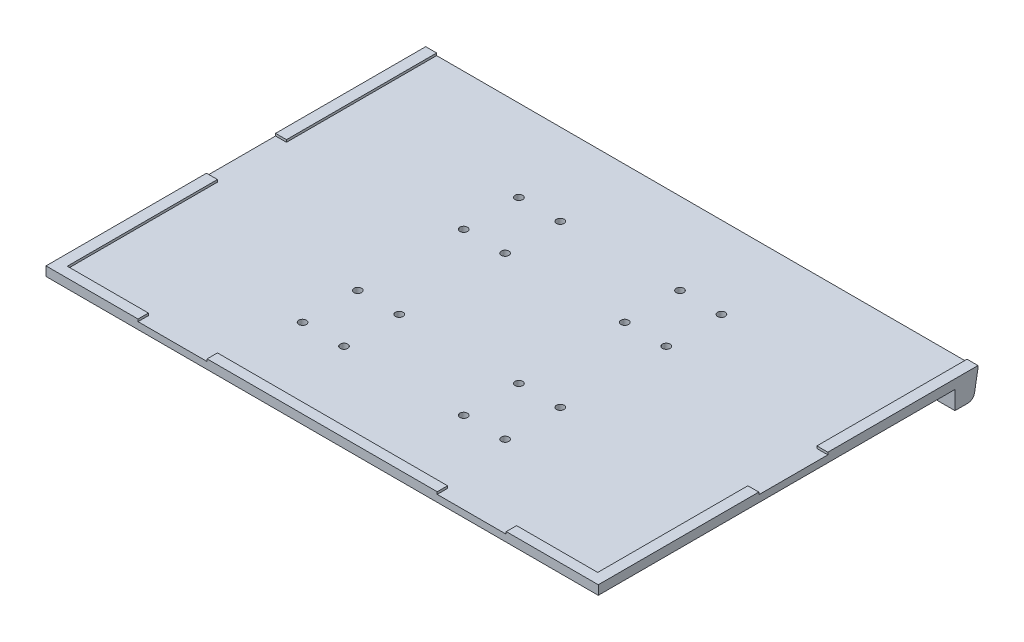
SolidWorks part; units mm, degrees
ref_plane "Front Plane" through (0, 0, 0) normal (0, 0, 1) x (1, 0, 0)
ref_plane "Top Plane" through (0, 0, 0) normal (0, 1, 0) x (1, 0, 0)
ref_plane "Right Plane" through (0, 0, 0) normal (1, 0, 0) x (0, 0, -1)
sketch "Sketch2" plane through (0, 0, 0) normal (0, 1, 0) x (1, 0, 0)
  line L0 (80, -78) -> (50, -78)
  line L1 (-120, 82.5) -> (120, 82.5)
  line L2 (-120, 82.5) -> (-120, -82.5)
  line L3 (-120, -82.5) -> (120, -82.5)
  line L4 (120, 82.5) -> (120, -82.5)
  line L5 (0, -82.5) -> (0, 82.5) construction
  line L6 (-120, 0) -> (120, 0) construction
  line L7 (-115.25, 82.5) -> (115.25, 82.5)
  line L8 (-115.25, 82.5) -> (-115.25, -78)
  line L9 (-115.25, -78) -> (115.25, -78)
  line L10 (115.25, 82.5) -> (115.25, -78)
  line L11 (0, -78) -> (0, 82.5) construction
  line L12 (-115.25, 2.25) -> (115.25, 2.25) construction
  line L13 (-80, -82.5) -> (-50, -82.5)
  line L14 (-80, -82.5) -> (-80, -78)
  line L15 (-80, -78) -> (-50, -78)
  line L16 (-50, -82.5) -> (-50, -78)
  line L17 (-65, -78) -> (-65, -82.5) construction
  line L18 (-80, -80.25) -> (-50, -80.25) construction
  line L19 (50, -82.5) -> (50, -78)
  line L20 (80, -82.5) -> (50, -82.5)
  line L21 (80, -82.5) -> (80, -78)
  line L22 (120, -12.75) -> (115.25, -12.75)
  line L23 (-120, 17.25) -> (-115.25, 17.25)
  line L24 (-120, 17.25) -> (-120, -12.75)
  line L25 (-120, -12.75) -> (-115.25, -12.75)
  line L26 (-115.25, 17.25) -> (-115.25, -12.75)
  line L27 (-117.625, -12.75) -> (-117.625, 17.25) construction
  line L28 (-120, 2.25) -> (-115.25, 2.25) construction
  line L29 (115.25, 17.25) -> (115.25, -12.75)
  line L30 (120, 17.25) -> (115.25, 17.25)
  line L31 (120, 17.25) -> (120, -12.75)
  line L33 (-35, 35) -> (35, 35) construction
  line L34 (-35, 35) -> (-35, -35) construction
  line L35 (-35, -35) -> (35, -35) construction
  line L36 (35, 35) -> (35, -35) construction
  line L37 (0, -35) -> (0, 35) construction
  line L38 (-35, 0) -> (35, 0) construction
  line L39 (-44, 47) -> (-26, 47) construction
  line L40 (-44, 47) -> (-44, 23) construction
  line L41 (-44, 23) -> (-26, 23) construction
  line L42 (-26, 47) -> (-26, 23) construction
  line L43 (-35, 23) -> (-35, 47) construction
  line L44 (-44, 35) -> (-26, 35) construction
  circle A0 centre (-44, 47) radius 1.65
  circle A1 centre (-26, 47) radius 1.65
  circle A2 centre (-26, 23) radius 1.65
  circle A3 centre (-44, 23) radius 1.65
  circle A4 centre (26, 47) radius 1.65
  circle A5 centre (44, 47) radius 1.65
  circle A6 centre (26, 23) radius 1.65
  circle A7 centre (44, 23) radius 1.65
  circle A8 centre (26, -23) radius 1.65
  circle A9 centre (44, -23) radius 1.65
  circle A10 centre (26, -47) radius 1.65
  circle A11 centre (44, -47) radius 1.65
  circle A12 centre (-44, -23) radius 1.65
  circle A13 centre (-26, -23) radius 1.65
  circle A14 centre (-44, -47) radius 1.65
  circle A15 centre (-26, -47) radius 1.65
  point P0 (0, 0)
  point P24 (0, 0)
  point P178 (0, 2.25)
  point P226 (-65, -80.25)
  point P315 (-117.625, 2.25)
  dimension "D13" = 3.3
  dimension "D1" = 165
  dimension "D2" = 240
  dimension "D3" = 160.5
  dimension "D4" = 230.5
  dimension "D5" = 30
  dimension "D6" = 50
  dimension "D7" = 160.5
  dimension "D8" = 30
  dimension "D9" = 70
  dimension "D10" = 70
  dimension "D11" = 24
  dimension "D12" = 18
  dimension "D16" = 70
  dimension "D17" = 70
  dimension "D14" = 2
  dimension "D15" = 2
extrude "Boss-Extrude3" add sketch "Sketch2" along normal blind 4 contours L2 L23 L8 L1 | L25 L2 L3 L14 L9 L8 | L3 L19 L9 L16 | L4 L22 L10 L9 L21 L3 | L30 L4 L1 L10 region at (97.625, 0, 78.8041) region at (0, 0, 80.25) region at (-80.8041, 0, 80.25) region at (117.625, 0, -49.875) region at (-117.625, 0, -49.875)
extrude "Boss-Extrude4" add sketch "Sketch2<5>" along normal blind 3 contours L10 L1 L8 L9 L0 A15 A14 A13 A12 A11 A10 A9 A8 A7 A6 A5 A4 A3 A2 A1 A0 | L2 L25 L8 L23 | L3 L16 L9 L14 | L3 L21 L0 L19 | L4 L30 L10 L22 region at (65, 0, 80.25) region at (0, 0, -2.2584) region at (-65, 0, 80.25) region at (117.625, 0, -2.25) region at (-117.625, 0, -2.25)
sketch "Sketch2<5>" plane through (0, 0, 0) normal (0, 1, 0) x (1, 0, 0) same geometry as "Sketch2"
sketch "Sketch3" plane through (0, 0, 0) normal (0, -1, 0) x (1, 0, 0)
  line L0 (-120, -82.5) -> (-120, 82.5) construction
  line L1 (120, -82.5) -> (-120, -82.5)
  line L2 (120, -82.5) -> (120, -72.5)
  line L3 (120, -72.5) -> (-120, -72.5)
  line L4 (-120, -82.5) -> (-120, -72.5)
  line L5 (0, -72.5) -> (0, -82.5) construction
  line L6 (120, -77.5) -> (-120, -77.5) construction
  point P432 (0, -77.5)
  dimension "D1" = 10
extrude "Boss-Extrude5" add sketch "Sketch3" along normal blind 8
sketch "Sketch4" plane through (120, 0, 0) normal (1, 0, 0) x (0, 0, -1)
  line L0 (82.5, 3) -> (80.5604, -8)
  line L1 (82.5, 4) -> (82.5, -8) construction
  line L2 (82.5, -8) -> (72.5, -8) construction
  line L3 (80.5604, -8) -> (82.5, -8)
  line L4 (82.5, -8) -> (82.5, 3)
  line L5 (82.5, 4) -> (17.25, 4) construction
  dimension "D1" = 1
  dimension "D2" = 10
extrude "Cut-Extrude1" cut sketch "Sketch4" against normal through all
fillet "Fillet2" radius 3 1 edges at (0, -8, -80.5604)
